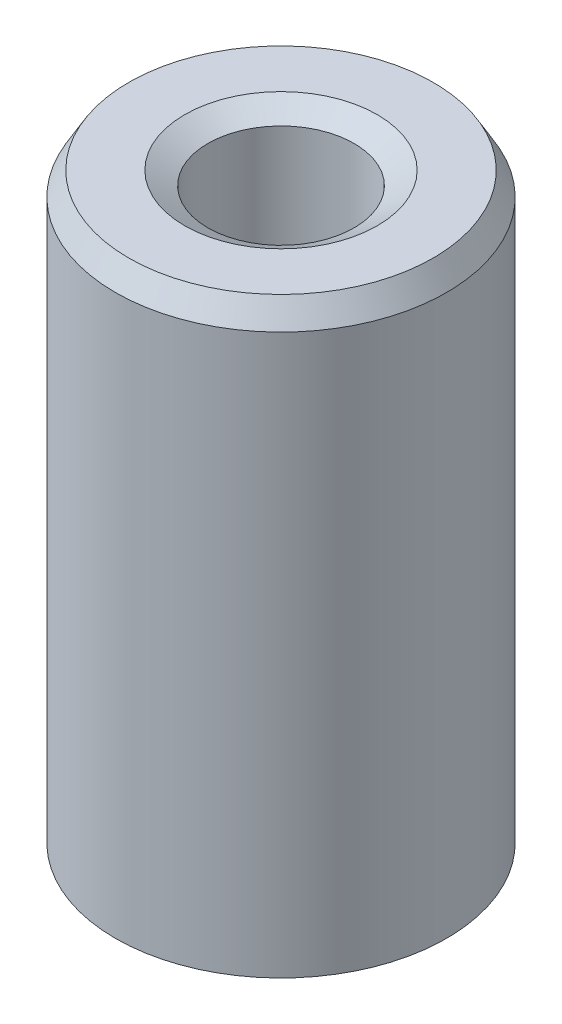
SolidWorks part; units mm, degrees
ref_plane "Front Plane" through (0, 0, 0) normal (0, 0, 1) x (1, 0, 0)
ref_plane "Top Plane" through (0, 0, 0) normal (0, 1, 0) x (1, 0, 0)
ref_plane "Right Plane" through (0, 0, 0) normal (1, 0, 0) x (0, 0, -1)
sketch "Sketch1" plane through (0, 0, 0) normal (0, 1, 0) x (1, 0, 0)
  circle A0 centre (0, 0) radius 22.5
  dimension "SLEEVE_OD" = 45
extrude "Boss-Extrude1" add sketch "Sketch1" along normal blind 80.9748
sketch "Sketch2" plane through (0, 0, 0) normal (0, 1, 0) x (1, 0, 0)
  circle A0 centre (0, 0) radius 9.9379
  dimension "BORE_D" = 19.8758
extrude "Cut-Extrude1" cut sketch "Sketch2" along normal through all
chamfer "Chamfer1" distance 3.1473 angle 30 4 edges at (0, 80.9748, 9.9379) (0, 0, 9.9379) (0, 0, 22.5) (0, 80.9748, 22.5) first distance on face at (0, 80.9748, 9.9379) first distance on face at (0, 0, 9.9379) first distance on face at (0, 80.9748, 22.5)
